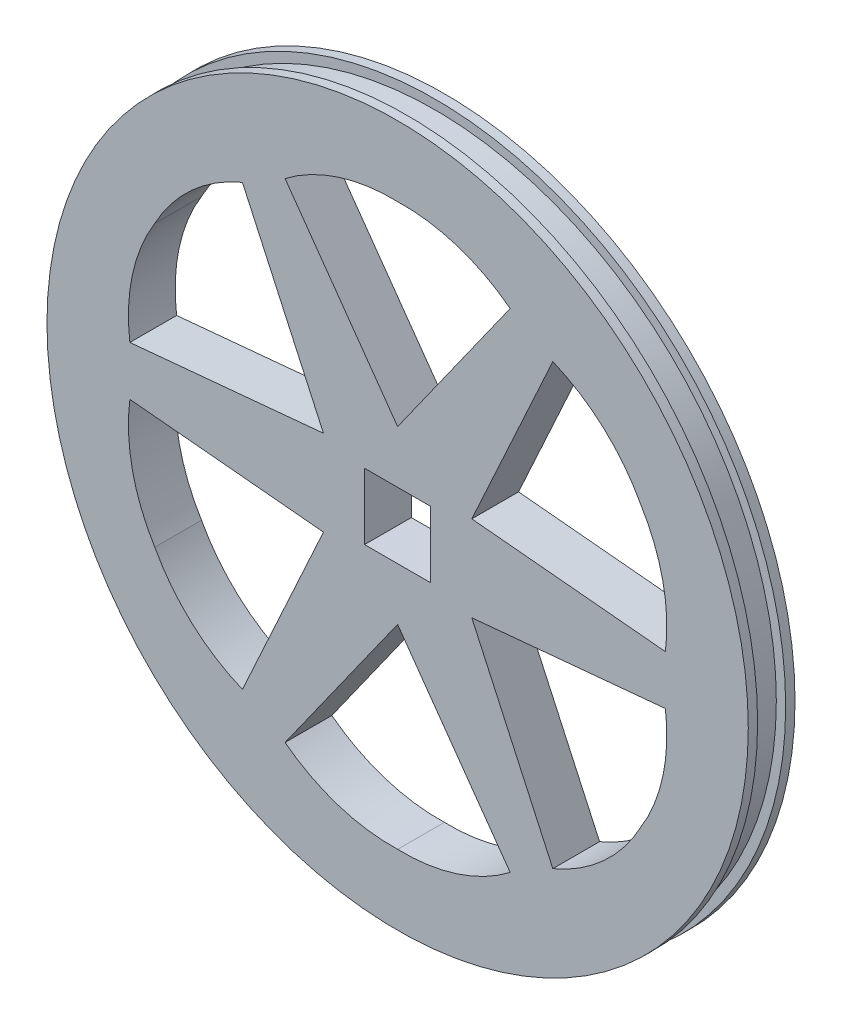
SolidWorks part; units mm, degrees
ref_plane "Front Plane" through (0, 0, 0) normal (0, 0, 1) x (1, 0, 0)
ref_plane "Top Plane" through (0, 0, 0) normal (0, 1, 0) x (1, 0, 0)
ref_plane "Right Plane" through (0, 0, 0) normal (1, 0, 0) x (0, 0, -1)
sketch "Sketch1" plane through (0, 0, 0) normal (0, 0, 1) x (1, 0, 0)
  line L1 (3.5355, -3.5355) -> (-3.5355, -3.5355)
  line L2 (3.5355, -3.5355) -> (3.5355, 3.5355)
  line L3 (3.5355, 3.5355) -> (-3.5355, 3.5355)
  line L4 (-3.5355, -3.5355) -> (-3.5355, 3.5355)
  line L5 (3.5355, -3.5355) -> (-3.5355, 3.5355) construction
  line L6 (3.5355, 3.5355) -> (-3.5355, -3.5355) construction
  circle A0 centre (0, 0) radius 37.5
  circle A1 centre (0, 0) radius 5 construction
  dimension "D1" = 75
  dimension "D2" = 10
extrude "Boss-Extrude1" add sketch "Sketch1" along normal mid plane 5
sketch "Sketch2" plane through (0, 0, 0) normal (0, 0, 1) x (1, 0, 0)
  line L0 (0, 0) -> (0, 32.5712) construction
  line L1 (0, 9.1586) -> (-12.0371, 26.1152)
  line L2 (0, 9.1586) -> (12.0371, 26.1152)
  arc A0 (-12.0371, 26.1152) -> (0, 29.9881) centre (-0.5568, 11.0765) cw
  arc A1 (12.0371, 26.1152) -> (0, 29.9881) centre (0.5568, 11.0765) ccw
extrude "Cut-Extrude1" cut sketch "Sketch2" along normal mid plane 8
pattern_circular "CirPattern1" count 6 over 360 about axis through (0, 0, 2.5) along (0, 0, -1) of "Cut-Extrude1" reverse direction yes
sketch "Sketch3" plane through (0, 0, 0) normal (0, 0, 1) x (1, 0, 0)
  circle A0 centre (0, 0) radius 37.5
  circle A1 centre (0, 0) radius 36.5
  circle A2 centre (0, 0) radius 37.5 construction
  dimension "D1" = 1
extrude "Cut-Extrude2" cut sketch "Sketch3" against normal mid plane 3
